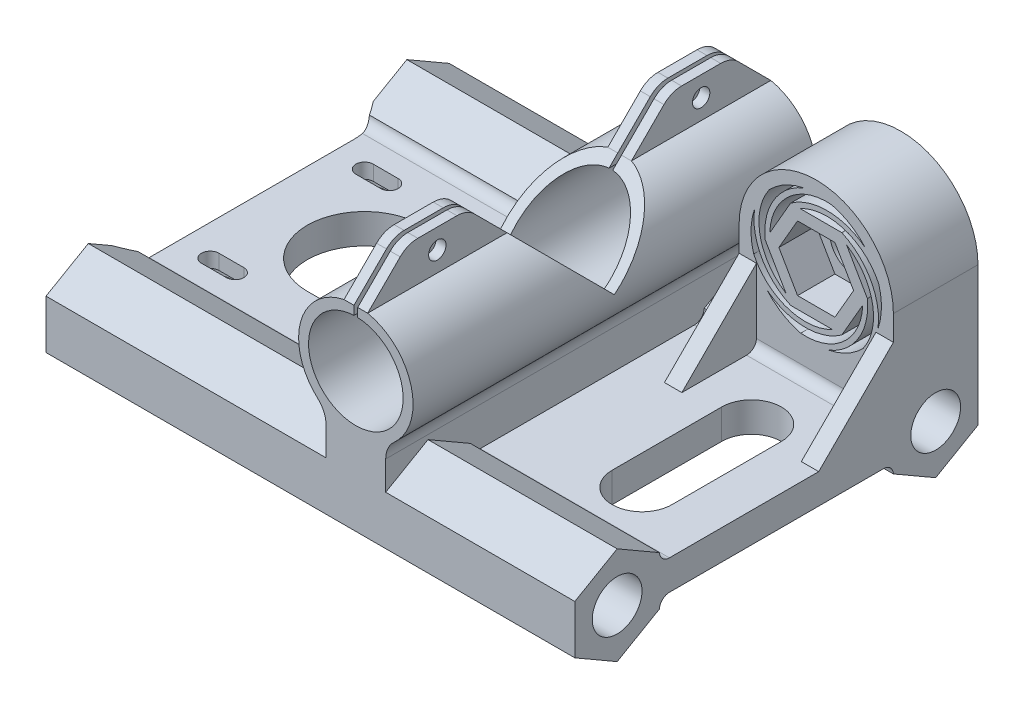
SolidWorks part; units mm, degrees
ref_plane "Front Plane" through (0, 0, 0) normal (0, 0, 1) x (1, 0, 0)
ref_plane "Top Plane" through (0, 0, 0) normal (0, 1, 0) x (1, 0, 0)
ref_plane "Right Plane" through (0, 0, 0) normal (1, 0, 0) x (0, 0, -1)
sketch "Sketch2" plane through (0, 0, 0) normal (1, 0, 0) x (0, 0, -1)
  line L0 (-5.6113, 0) -> (58.3887, 0) construction
  line L1 (2.8887, 3) -> (49.8887, 3)
  line L2 (66.8887, 4.9075) -> (58.3887, 9.815)
  line L3 (58.3887, 9.815) -> (49.8887, 4.9075)
  line L4 (49.8887, 4.9075) -> (49.8887, 3)
  line L5 (49.8887, -4.9075) -> (58.3887, -9.815)
  line L6 (58.3887, -9.815) -> (66.8887, -4.9075)
  line L7 (66.8887, -4.9075) -> (66.8887, 4.9075)
  line L8 (2.8887, 4.9075) -> (-5.6113, 9.815)
  line L9 (-5.6113, 9.815) -> (-14.1113, 4.9075)
  line L10 (-14.1113, 4.9075) -> (-14.1113, -4.9075)
  line L11 (-14.1113, -4.9075) -> (-5.6113, -9.815)
  line L12 (-5.6113, -9.815) -> (2.8887, -4.9075)
  line L13 (2.8887, -4.9075) -> (2.8887, -3)
  line L14 (2.8887, -3) -> (49.8887, -3)
  line L15 (49.8887, -3) -> (49.8887, -4.9075)
  line L16 (2.8887, 3) -> (2.8887, 4.9075)
  circle A2 centre (58.3887, 0) radius 8.5 construction
  circle A3 centre (-5.6113, 0) radius 8.5 construction
  dimension "D2" = 17
  dimension "D3" = 47
  dimension "D4" = 6
  dimension "D5" = 3
extrude "Boss-Extrude1" add sketch "Sketch2" along normal blind 106.25
sketch "Sketch3" plane through (0, 3, 0) normal (0, 1, 0) x (1, 0, 0)
  line L0 (0, 49.8887) -> (47, 2.8887) construction
  line L1 (106.25, 2.8887) -> (0, 2.8887) construction
  line L2 (0, 2.8887) -> (47, 49.8887) construction
  line L3 (106.25, 49.8887) -> (0, 49.8887) construction
  line L4 (106.25, 2.8887) -> (0, 2.8887) construction
  line L5 (1.75, 48.1387) -> (1.75, 2.8887)
  line L6 (39, 41.8887) -> (8, 41.8887) construction
  line L7 (39, 41.8887) -> (39, 10.8887) construction
  line L8 (39, 10.8887) -> (8, 10.8887) construction
  line L9 (8, 41.8887) -> (8, 10.8887) construction
  line L10 (1.75, 48.1387) -> (45.25, 48.1387) construction
  line L11 (45.25, 48.1387) -> (45.25, 4.6387) construction
  line L12 (45.25, 4.6387) -> (1.75, 4.6387) construction
  line L13 (1.75, 2.8887) -> (0, -0.8613)
  line L14 (0, 2.8887) -> (0, -5.6113) construction
  line L15 (8, 41.8887) -> (13, 41.8887) construction
  line L16 (1.75, 48.1387) -> (1.75, 49.8887)
  line L17 (8, 43.6387) -> (13, 43.6387)
  line L18 (1.75, 49.8887) -> (0, 51.6387)
  line L19 (8, 40.1387) -> (13, 40.1387)
  line L20 (0, 58.3887) -> (0, 49.8887) construction
  line L21 (0, 51.6387) -> (0, -0.8613)
  line L22 (39, 41.8887) -> (44, 41.8887) construction
  line L23 (39, 43.6387) -> (44, 43.6387)
  line L24 (39, 40.1387) -> (44, 40.1387)
  line L25 (39, 10.8887) -> (44, 10.8887) construction
  line L26 (39, 12.6387) -> (44, 12.6387)
  line L27 (39, 9.1387) -> (44, 9.1387)
  line L28 (8, 10.8887) -> (13, 10.8887) construction
  line L29 (8, 12.6387) -> (13, 12.6387)
  line L30 (8, 9.1387) -> (13, 9.1387)
  line L31 (23.5, 26.3887) -> (28.5, 26.3887) construction
  line L32 (23.5, 37.8887) -> (28.5, 37.8887)
  line L33 (23.5, 14.8887) -> (28.5, 14.8887)
  circle A0 centre (23.5, 26.3887) radius 11.5 construction
  circle A1 centre (39, 41.8887) radius 1.75 construction
  circle A2 centre (39, 10.8887) radius 1.75 construction
  circle A3 centre (8, 10.8887) radius 1.75 construction
  circle A4 centre (8, 41.8887) radius 1.75 construction
  arc A5 (8, 43.6387) -> (8, 40.1387) centre (8, 41.8887) ccw
  arc A6 (13, 40.1387) -> (13, 43.6387) centre (13, 41.8887) ccw
  arc A7 (39, 43.6387) -> (39, 40.1387) centre (39, 41.8887) ccw
  arc A8 (44, 40.1387) -> (44, 43.6387) centre (44, 41.8887) ccw
  arc A9 (39, 12.6387) -> (39, 9.1387) centre (39, 10.8887) ccw
  arc A10 (44, 9.1387) -> (44, 12.6387) centre (44, 10.8887) ccw
  arc A11 (8, 12.6387) -> (8, 9.1387) centre (8, 10.8887) ccw
  arc A12 (13, 9.1387) -> (13, 12.6387) centre (13, 10.8887) ccw
  arc A13 (23.5, 37.8887) -> (23.5, 14.8887) centre (23.5, 26.3887) ccw
  arc A14 (28.5, 14.8887) -> (28.5, 37.8887) centre (28.5, 26.3887) ccw
  point P24 (10.5, 41.8887)
  point P40 (41.5, 41.8887)
  point P46 (41.5, 10.8887)
  point P52 (10.5, 10.8887)
  point P58 (26, 26.3887)
  dimension "D4" = 3.5
  dimension "D5" = 23
  dimension "D12" = 1.75
  dimension "D13" = 11.5
  dimension "D1" = 45
  dimension "D2" = 45
  dimension "D3" = 31
  dimension "D6" = 43.5
  dimension "D7" = 5
  dimension "D8" = 5
  dimension "D9" = 5
  dimension "D10" = 5
  dimension "D11" = 5
extrude "Cut-Extrude1" cut sketch "Sketch3" against normal blind 28 and the other way blind 30
fillet "Fillet3" radius 2 4 edges at (54, -3, -2.8887) (54, -3, -49.8887) (54, 3, -49.8887) (54, 3, -2.8887)
sketch "Sketch4" plane through (0, 0, -66.8887) normal (0, 0, -1) x (-1, 0, 0)
  line L0 (-62.25, 3) -> (-62.25, 23) construction
  line L1 (-106.25, 3) -> (-1.75, 3) construction
  line L3 (-68.25, 3) -> (-68.25, 13.1893)
  line L4 (-56.25, 3) -> (-56.25, 13.1893)
  line L5 (-56.25, 3) -> (-68.25, 3)
  line L6 (-59.875, 34.2521) -> (-59.875, 42.2521)
  line L7 (-59.875, 42.2521) -> (-61.875, 42.2521)
  line L8 (-61.875, 42.2521) -> (-61.875, 32.4926)
  line L9 (-64.625, 34.2521) -> (-64.625, 42.2521)
  line L10 (-64.625, 42.2521) -> (-62.625, 42.2521)
  line L11 (-62.625, 42.2521) -> (-62.625, 32.4926)
  line L12 (-1.75, 4.9075) -> (-1.75, -4.9075) construction
  arc A0 (-62.625, 32.4926) -> (-61.875, 32.4926) centre (-62.25, 23) ccw
  arc A1 (-56.25, 13.1893) -> (-59.875, 34.2521) centre (-62.25, 23) ccw
  arc A3 (-64.625, 34.2521) -> (-68.25, 13.1893) centre (-62.25, 23) ccw
  dimension "D1" = 2
  dimension "D2" = 2
  dimension "D3" = 0.75
  dimension "D10" = 8
  dimension "D6" = 19
  dimension "D7" = 23
  dimension "D4" = 12
  dimension "D5" = 6
  dimension "D8" = 20
  dimension "D9" = 0.375
  dimension "D11" = 60.5
extrude "Boss-Extrude2" add sketch "Sketch4" against normal up to surface (81 mm away) up to face at (53.125, 0, 14.1113)
fillet "Fillet4" radius 5 2 edges at (56.25, 13.1893, -26.3887) (68.25, 13.1893, -26.3887)
sketch "Sketch5" plane through (0, 0, -66.8887) normal (0, 0, -1) x (-1, 0, 0)
  line L0 (-62.25, 23) -> (-110, 23) construction
  line L1 (-106.25, 23) -> (-106.25, 4.9075)
  line L2 (-106.25, 4.9075) -> (-68.25, 4.9075) construction
  line L3 (-106.25, 4.9075) -> (-75.25, 4.9075)
  line L4 (-75.25, 4.9075) -> (-75.25, 23)
  circle A0 centre (-90.75, 23) radius 4.75
  arc A1 (-75.25, 23) -> (-106.25, 23) centre (-90.75, 23) ccw
  arc A2 (-62.625, 32.4926) -> (-61.875, 32.4926) centre (-62.25, 23) ccw construction
  dimension "D1" = 9.5
  dimension "D3" = 31
  dimension "D4" = 0
  dimension "D5" = 28.5
  dimension "D2" = 28.5
extrude "Boss-Extrude7" add sketch "Sketch5" against normal up to vertex (17 mm away) up to point (68.25, 4.9075, -49.8887)
sketch "Sketch6" plane through (0, 0, -49.8887) normal (0, 0, 1) x (1, 0, 0)
  line L0 (106.25, 9.815) -> (68.25, 9.815) construction
  line L1 (83.2444, 23) -> (86.9972, 16.5)
  line L2 (86.9972, 16.5) -> (94.5028, 16.5)
  line L3 (94.5028, 16.5) -> (98.2556, 23)
  line L4 (98.2556, 23) -> (94.5028, 29.5)
  line L5 (94.5028, 29.5) -> (86.9972, 29.5)
  line L6 (86.9972, 29.5) -> (83.2444, 23)
  circle A0 centre (90.75, 23) radius 6.5 construction
  dimension "D1" = 13
extrude "Cut-Extrude2" cut sketch "Sketch6" against normal blind 7.5
sketch "Sketch7" plane through (0, 0, 0) normal (-1, 0, 0) x (0, 0, 1)
  line L0 (14.1113, 42.2521) -> (-66.8887, 42.2521) construction
  line L1 (-66.8887, 34.2521) -> (-38.8887, 34.2521) construction
  line L2 (-66.8887, 34.2521) -> (-66.8887, 14.4284) construction
  line L3 (-66.8887, 14.4284) -> (-38.8887, 14.4284) construction
  line L4 (-38.8887, 34.2521) -> (-38.8887, 14.4284) construction
  line L6 (14.1113, 14.4284) -> (-13.8887, 14.4284) construction
  line L7 (14.1113, 14.4284) -> (14.1113, 34.2521) construction
  line L8 (14.1113, 34.2521) -> (-13.8887, 34.2521) construction
  line L9 (-13.8887, 14.4284) -> (-13.8887, 34.2521) construction
  line L10 (14.1113, 38.2521) -> (-67.3887, 38.2521) construction
  line L11 (14.1113, 14.4284) -> (14.1113, 34.2521) construction
  line L12 (-38.8887, 42.2521) -> (-66.8887, 42.2521) construction
  line L13 (-52.8887, 34.2521) -> (-52.8887, 42.2521) construction
  line L15 (0.1113, 34.2521) -> (0.1113, 42.2521) construction
  line L16 (-38.8887, 34.2521) -> (-26.3887, 21.7521)
  line L17 (-13.8887, 34.2521) -> (-26.3887, 21.7521)
  line L18 (-13.8887, 34.2521) -> (-13.8887, 42.2521)
  line L19 (-38.8887, 34.2521) -> (-38.8887, 42.2521)
  line L20 (-38.8887, 42.2521) -> (-13.8887, 42.2521)
  line L21 (-66.8887, 14.4284) -> (14.1113, 14.4284) construction
  line L22 (-13.8887, 42.2521) -> (14.1113, 42.2521) construction
  line L25 (14.1113, 42.2521) -> (14.1113, 34.2521) construction
  line L26 (14.1113, 34.2521) -> (-66.8887, 34.2521) construction
  circle A0 centre (0.1113, 38.2521) radius 1.75
  circle A1 centre (-52.8887, 38.2521) radius 1.75
  dimension "D3" = 3.5
  dimension "D1" = 28
  dimension "D2" = 28
  dimension "D4" = 45
  dimension "D5" = 45
extrude "Cut-Extrude3" cut sketch "Sketch7" against normal up to surface (75.25 mm away) up to face at (75.25, 13.126, -58.3887)
chamfer "Chamfer1" distance 8 angle 45 8 edges at (60.875, 42.2521, -66.8887) (63.625, 42.2521, -66.8887) (63.625, 42.2521, -38.8887) (60.875, 42.2521, -38.8887) (63.625, 42.2521, 14.1113) (60.875, 42.2521, 14.1113) (60.875, 42.2521, -13.8887) (63.625, 42.2521, -13.8887)
fillet "Fillet5" radius 5 8 edges at (60.875, 42.2521, 6.1113) (63.625, 42.2521, 6.1113) (63.625, 42.2521, -5.8887) (60.875, 42.2521, -5.8887) (60.875, 42.2521, -46.8887) (63.625, 42.2521, -46.8887) (63.625, 42.2521, -58.8887) (60.875, 42.2521, -58.8887)
sketch "Sketch9" plane through (106.25, 0, 0) normal (1, 0, 0) x (0, 0, -1)
  line L0 (-9.8613, 7.3612) -> (-1.3613, -7.3612) construction
  line L1 (-5.6113, 9.815) -> (-14.1113, 4.9075) construction
  line L2 (-5.6113, -9.815) -> (2.8887, -4.9075) construction
  line L3 (54.1387, -7.3612) -> (62.6387, 7.3612) construction
  line L4 (49.8887, -4.9075) -> (58.3887, -9.815) construction
  circle A0 centre (58.3887, 0) radius 5
  circle A1 centre (-5.6113, 0) radius 5
  dimension "D1" = 10
extrude "Cut-Extrude5" cut sketch "Sketch9" against normal up to surface (50 mm away) up to face at (56.25, 6.5862, -26.3887)
sketch "Sketch14" plane through (0, 3, 0) normal (0, 1, 0) x (1, 0, 0)
  line L0 (91.25, 64.8887) -> (91.25, -14.1113) construction
  line L3 (106.25, 47.8909) -> (106.25, 4.8866) construction
  line L4 (91.25, 36.3887) -> (91.25, 14.3887) construction
  line L5 (97.25, 36.3887) -> (97.25, 14.3887)
  line L6 (85.25, 36.3887) -> (85.25, 14.3887)
  line L8 (106.25, -14.1113) -> (68.25, -14.1113) construction
  arc A0 (97.25, 36.3887) -> (85.25, 36.3887) centre (91.25, 36.3887) ccw
  arc A1 (85.25, 14.3887) -> (97.25, 14.3887) centre (91.25, 14.3887) ccw
  point P10 (91.25, 25.3887)
  dimension "D2" = 6
  dimension "D1" = 15
  dimension "D3" = 22
extrude "Cut-Extrude8" cut sketch "Sketch14" against normal blind 10
fillet "Fillet7" radius 10 2 edges at (1.75, 0, -2.8887) (1.75, 0, -49.8887)
sketch "Sketch16" plane through (106.25, 0, 0) normal (1, 0, 0) x (0, 0, -1)
  line L0 (49.8887, 18) -> (49.8887, 3)
  line L1 (49.8887, 23) -> (49.8887, 4.9075) construction
  line L3 (49.8887, 3) -> (34.8887, 3)
  line L4 (47.8909, 3) -> (4.8866, 3) construction
  line L5 (34.8887, 3) -> (49.8887, 18)
  dimension "D1" = 15
extrude "Boss-Extrude8" add sketch "Sketch16" against normal blind 3.5
sketch "Sketch17" plane through (75.25, 0, 0) normal (-1, 0, 0) x (0, 0, 1)
  line L0 (-49.8887, 18) -> (-34.8887, 3)
  line L1 (-34.8887, 3) -> (-49.8887, 3)
  line L2 (-49.8887, 3) -> (-49.8887, 18)
extrude "Boss-Extrude9" add sketch "Sketch17" against normal blind 3.5
sketch "Sketch18" plane through (0, 0, -49.8887) normal (0, 0, 1) x (1, 0, 0)
  line L0 (98.2556, 23) -> (94.5028, 29.5) construction
  line L1 (101.0268, 23) -> (95.8884, 31.9) construction
  line L2 (95.8884, 31.9) -> (85.6116, 31.9) construction
  line L3 (85.6116, 31.9) -> (80.4732, 23) construction
  line L4 (80.4732, 23) -> (85.6116, 14.1) construction
  line L5 (85.6116, 14.1) -> (95.8884, 14.1) construction
  line L6 (95.8884, 14.1) -> (101.0268, 23) construction
  line L7 (94.5028, 29.5) -> (86.9972, 29.5) construction
  line L8 (96.8303, 30.2686) -> (101.0268, 23)
  line L9 (100.0849, 21.3686) -> (95.8884, 14.1)
  line L10 (94.0046, 14.1) -> (85.6116, 14.1)
  line L11 (84.6697, 15.7314) -> (80.4732, 23)
  line L12 (81.4151, 24.6314) -> (85.6116, 31.9)
  line L13 (87.4954, 31.9) -> (95.8884, 31.9)
  circle A0 centre (90.75, 23) radius 8.9 construction
  arc A1 (100.6263, 31.6063) -> (93.8706, 35.7229) centre (90.75, 23) ccw construction
  arc A2 (106.25, 23) -> (75.25, 23) centre (90.75, 23) ccw construction
  arc A3 (95.8884, 31.9) -> (101.0292, 13.3654) centre (90.7643, 20.4985) cw construction
  arc A4 (95.8884, 31.9) -> (103.1414, 18.75) centre (90.7643, 20.4985) cw
  arc A5 (96.8303, 30.2686) -> (100.208, 13.936) centre (90.7643, 20.4985) cw
  arc A6 (95.4785, 30.9879) -> (100.208, 13.936) centre (90.7643, 20.4985) cw construction
  arc A7 (101.0268, 23) -> (93.2651, 10.1437) centre (88.5908, 21.7369) cw
  arc A8 (100.0849, 21.3686) -> (87.6294, 10.2771) centre (88.5908, 21.7369) cw
  arc A9 (95.8884, 14.1) -> (80.8737, 14.3937) centre (88.5765, 24.2383) cw
  arc A10 (94.0046, 14.1) -> (78.1714, 19.3411) centre (88.5765, 24.2383) cw
  arc A11 (85.6116, 14.1) -> (78.3586, 27.25) centre (90.7357, 25.5015) cw
  arc A12 (84.6697, 15.7314) -> (81.292, 32.064) centre (90.7357, 25.5015) cw
  arc A13 (80.4732, 23) -> (88.2349, 35.8563) centre (92.9092, 24.2631) cw
  arc A14 (81.4151, 24.6314) -> (93.8706, 35.7229) centre (92.9092, 24.2631) cw
  arc A15 (85.6116, 31.9) -> (100.6263, 31.6063) centre (92.9235, 21.7617) cw
  arc A16 (87.4954, 31.9) -> (103.3286, 26.6589) centre (92.9235, 21.7617) cw
  arc A17 (100.6263, 31.6063) -> (93.8706, 35.7229) centre (90.75, 23) ccw
  arc A18 (88.2349, 35.8563) -> (81.292, 32.064) centre (90.75, 23) ccw construction
  arc A19 (88.2349, 35.8563) -> (81.292, 32.064) centre (90.75, 23) ccw
  arc A20 (78.3586, 27.25) -> (78.1714, 19.3411) centre (90.75, 23) ccw construction
  arc A21 (78.3586, 27.25) -> (78.1714, 19.3411) centre (90.75, 23) ccw
  arc A22 (80.8737, 14.3937) -> (87.6294, 10.2771) centre (90.75, 23) ccw construction
  arc A23 (80.8737, 14.3937) -> (87.6294, 10.2771) centre (90.75, 23) ccw
  arc A24 (93.2651, 10.1437) -> (100.208, 13.936) centre (90.75, 23) ccw construction
  arc A25 (93.2651, 10.1437) -> (100.208, 13.936) centre (90.75, 23) ccw
  arc A26 (103.1414, 18.75) -> (103.3286, 26.6589) centre (90.75, 23) ccw construction
  arc A27 (103.1414, 18.75) -> (103.3286, 26.6589) centre (90.75, 23) ccw
  point P56 (90.75, 23)
  dimension "D1" = 2.4
  dimension "D3" = 4.25
  dimension "D5" = 12.5
  dimension "D2" = 2.4
  dimension "D4" = 1
extrude "Cut-Extrude9" cut sketch "Sketch18" against normal up to surface (17 mm away) up to face at (61.6667, 17.1213, -66.8887)
sketch "Sketch20" plane through (0, -3, 0) normal (0, -1, 0) x (1, 0, 0)
  line L0 (8, -10.8887) -> (13, -10.8887) construction
  line L1 (8, -6.3887) -> (13, -6.3887)
  line L2 (8, -15.3887) -> (13, -15.3887)
  line L3 (39, -10.8887) -> (44, -10.8887) construction
  line L4 (39, -6.3887) -> (44, -6.3887)
  line L5 (39, -15.3887) -> (44, -15.3887)
  line L6 (39, -41.8887) -> (44, -41.8887) construction
  line L7 (39, -37.3887) -> (44, -37.3887)
  line L8 (39, -46.3887) -> (44, -46.3887)
  line L9 (13, -41.8887) -> (8, -41.8887) construction
  line L10 (13, -46.3887) -> (8, -46.3887)
  line L11 (13, -37.3887) -> (8, -37.3887)
  arc A0 (8, -6.3887) -> (8, -15.3887) centre (8, -10.8887) ccw
  arc A1 (13, -15.3887) -> (13, -6.3887) centre (13, -10.8887) ccw
  arc A2 (39, -6.3887) -> (39, -15.3887) centre (39, -10.8887) ccw
  arc A3 (44, -15.3887) -> (44, -6.3887) centre (44, -10.8887) ccw
  arc A4 (39, -37.3887) -> (39, -46.3887) centre (39, -41.8887) ccw
  arc A5 (44, -46.3887) -> (44, -37.3887) centre (44, -41.8887) ccw
  arc A6 (13, -46.3887) -> (13, -37.3887) centre (13, -41.8887) ccw
  arc A7 (8, -37.3887) -> (8, -46.3887) centre (8, -41.8887) ccw
  point P4 (10.5, -10.8887)
  point P9 (41.5, -10.8887)
  point P18 (41.5, -41.8887)
  point P27 (10.5, -41.8887)
  dimension "D1" = 4.5
extrude "Cut-Extrude10" cut sketch "Sketch20" against normal blind 3
